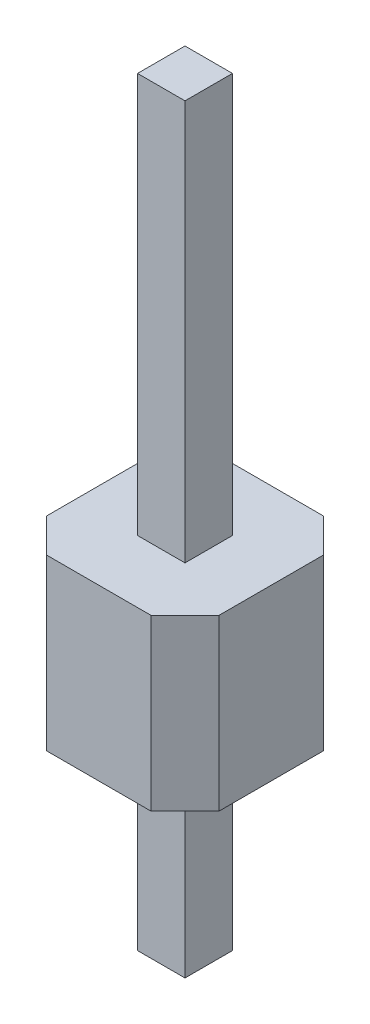
SolidWorks part; units mm, degrees
material "201 Annealed Stainless Steel (SS)"
ref_plane "Front Plane" through (0, 0, 0) normal (0, 0, 1) x (1, 0, 0)
ref_plane "Top Plane" through (0, 0, 0) normal (0, 1, 0) x (1, 0, 0)
ref_plane "Right Plane" through (0, 0, 0) normal (1, 0, 0) x (0, 0, -1)
sketch "Sketch1" plane through (0, 0, 0) normal (0, 1, 0) x (1, 0, 0)
  line L1 (0, 0) -> (2.54, 0)
  line L2 (0, 0) -> (0, 2.54)
  line L3 (0, 2.54) -> (2.54, 2.54)
  line L4 (2.54, 0) -> (2.54, 2.54)
  line L5 (0.92, 1.62) -> (1.62, 1.62)
  line L6 (0.92, 1.62) -> (0.92, 0.92)
  line L7 (0.92, 0.92) -> (1.62, 0.92)
  line L8 (1.62, 1.62) -> (1.62, 0.92)
  dimension "D1" = 2.54
  dimension "D2" = 0.7
  dimension "D3" = 0.92
  dimension "D4" = 0.92
extrude "Boss-Extrude1" add sketch "Sketch1" along normal blind 11.2 contours L8 L5 L6 L7 region at (1.27, 0, -1.27)
extrude "Boss-Extrude2" add sketch "Sketch1<3>" along normal blind 2.5 from offset 2.8 contours L1 L4 L3 L2 L5 L8 L7 L6 region at (0.0359, 0, -1.27)
sketch "Sketch1<3>" plane through (0, 0, 0) normal (0, 1, 0) x (1, 0, 0) same geometry as "Sketch1"
chamfer "Chamfer1" distance 0.5 angle 45 4 edges at (0, 4.05, 0) (0, 4.05, -2.54) (2.54, 4.05, 0) (2.54, 4.05, -2.54)
